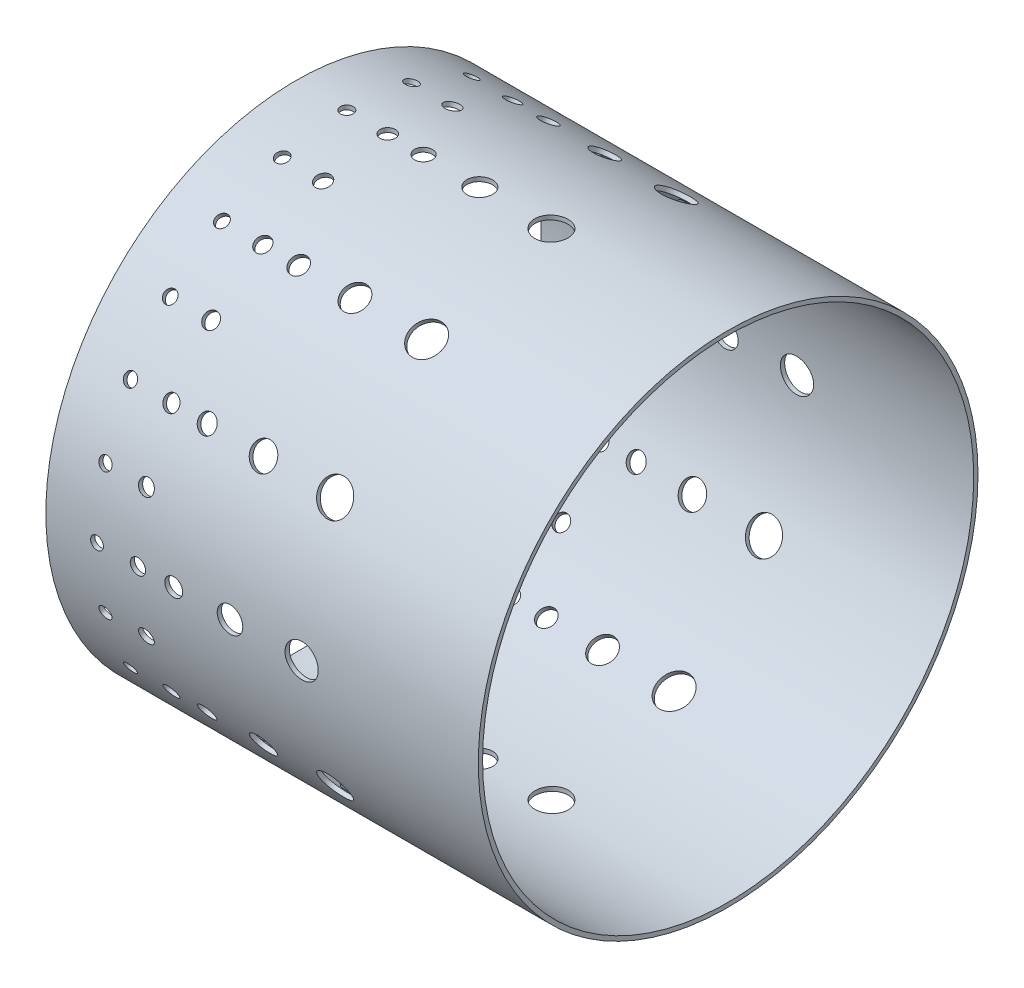
SolidWorks part; units mm, degrees
material "201 Annealed Stainless Steel (SS)"
ref_plane "Front Plane" through (0, 0, 0) normal (0, 0, 1) x (1, 0, 0)
ref_plane "Top Plane" through (0, 0, 0) normal (0, 1, 0) x (1, 0, 0)
ref_plane "Right Plane" through (0, 0, 0) normal (1, 0, 0) x (0, 0, -1)
sketch "Sketch1" plane through (0, 0, 0) normal (1, 0, 0) x (0, 0, -1)
  circle A0 centre (0, 0) radius 48.8442
  circle A1 centre (0, 0) radius 48.006
  dimension "D1" = 0.8382
  dimension "D2" = 96.012
extrude "Boss-Extrude1" add sketch "Sketch1" along normal blind 84.5439
sketch "Sketch3" plane through (0, 0, 0) normal (0, 1, 0) x (1, 0, 0)
  line L0 (0, 0) -> (118.8164, 0) construction
  line L1 (0, 48.8442) -> (0, -48.8442) construction
sketch "Sketch2" plane through (0, 0, 0) normal (0, 1, 0) x (1, 0, 0)
  line L0 (0, 0) -> (89.7894, 0) construction
  line L1 (0, 48.8442) -> (0, -48.8442) construction
  circle A0 centre (10, 0) radius 1.25
  dimension "D2" = 2.5
  dimension "D1" = 10
extrude "Cut-Extrude1" cut sketch "Sketch2" against normal through all
pattern_circular "CirPattern1" count 24 over 360 about axis through (0, 0, 0) along (1, 0, 0) of "Cut-Extrude1"
sketch "Sketch4" plane through (0, 0, 0) normal (0, 0, 1) x (1, 0, 0)
  line L0 (0, 0) -> (118.8164, 0) construction
  circle A0 centre (18, 0) radius 1.5
  dimension "D1" = 18
  dimension "D2" = 3
extrude "Cut-Extrude2" cut sketch "Sketch4" against normal through all
pattern_circular "CirPattern2" count 24 over 360 about axis through (0, 0, 0) along (1, 0, 0) of "Cut-Extrude2" reverse direction yes
sketch "Sketch5" plane through (0, 0, 0) normal (0, 0, 1) x (1, 0, 0)
  line L0 (0, 0) -> (118.8164, 0) construction
  line L1 (0, 48.8442) -> (0, -48.8442) construction
  circle A0 centre (25, 0) radius 1.75
  dimension "D2" = 3.5
  dimension "D1" = 25
extrude "Cut-Extrude3" cut sketch "Sketch5" against normal through all
pattern_circular "CirPattern3" count 12 over 360 about axis through (0, 0, 0) along (1, 0, 0) of "Cut-Extrude3"
sketch "Sketch6" plane through (0, 0, 0) normal (0, 0, 1) x (1, 0, 0)
  line L0 (0, 0) -> (118.8164, 0) construction
  line L1 (0, 48.8442) -> (0, -48.8442) construction
  circle A0 centre (36, 0) radius 2.5
  dimension "D2" = 5
  dimension "D1" = 36
extrude "Cut-Extrude4" cut sketch "Sketch6" against normal through all
pattern_circular "CirPattern4" count 12 over 360 about axis through (0, 0, 0) along (1, 0, 0) of "Cut-Extrude4"
sketch "Sketch7" plane through (0, 0, 0) normal (0, 1, 0) x (1, 0, 0)
  line L0 (0, 0) -> (118.8164, 0) construction
  circle A0 centre (50, 0) radius 3.25
  dimension "D1" = 50
  dimension "D2" = 6.5
extrude "Cut-Extrude5" cut sketch "Sketch7" against normal through all
pattern_circular "CirPattern5" count 12 over 360 about axis through (84.5439, 0, 0) along (-1, 0, 0) of "Cut-Extrude5"
